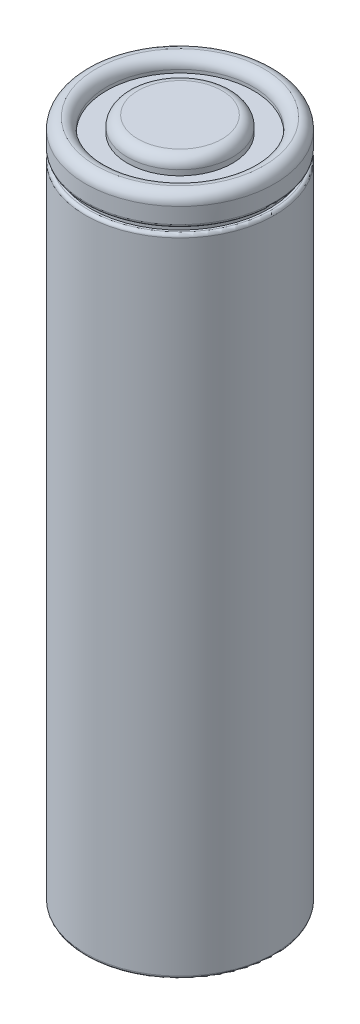
SolidWorks part; units mm, degrees
material "Chrome Stainless Steel"
ref_plane "Front Plane" through (0, 0, 0) normal (0, 0, 1) x (1, 0, 0)
ref_plane "Top Plane" through (0, 0, 0) normal (0, 1, 0) x (1, 0, 0)
ref_plane "Right Plane" through (0, 0, 0) normal (1, 0, 0) x (0, 0, -1)
sketch "Sketch1" plane through (0, 0, 0) normal (0, 1, 0) x (1, 0, 0)
  circle A0 centre (0, 0) radius 9
  dimension "D1" = 18
extrude "Boss-Extrude1" add sketch "Sketch1" along normal blind 65
sketch "Sketch2" plane through (0, 0, 0) normal (0, 0, 1) x (1, 0, 0)
  line L1 (0, 65) -> (0, 0) construction
  line L2 (9, 65) -> (-9, 65) construction
  line L3 (5, 65) -> (5, 63.5)
  line L4 (5, 63.5) -> (7, 63.5)
  line L5 (9, 0) -> (9, 65) construction
  line L6 (7, 63.5) -> (7, 64.8)
  line L7 (8.5, 62) -> (9, 62)
  line L8 (8.5, 62) -> (8.5, 61.5)
  line L9 (8.5, 61.5) -> (9, 61.5)
  line L10 (9, 62) -> (9, 61.5)
  line L11 (7, 64.8) -> (9, 64.8)
  line L12 (9, 64.8) -> (9, 65)
  line L13 (9, 65) -> (5, 65)
  dimension "D1" = 0.5
  dimension "D2" = 0.5
  dimension "D3" = 3
  dimension "D4" = 4
  dimension "D5" = 2
  dimension "D6" = 1.5
  dimension "D7" = 0.2
revolve "Cut-Revolve1" cut sketch "Sketch2" angle 360 about L1
fillet "Fillet1" radius 1 3 edges at (0, 65, 5) (0, 64.8, 7) (0, 64.8, 9)
fillet "Fillet2" radius 0.3 3 edges at (0, 0, 9) (0, 61.5, 9) (0, 62, 9)
equation "\"ABS_thickness\" = 1.59 "
equation "\"Bus_bar_thickness\" = 3.175"
equation "\"Connector_width\" = 20.2"
equation "\"Number_of_cells_long\" = 25"
equation "\"Number_of_cells_wide\" = 2"
equation "\"Cell_height\" = 65.0"
equation "\"D1@Sketch1\"  = \"Cell_diam\""
equation "\"Cell_diam\" = 18.0"
equation "\"D1@Boss-Extrude1\"=\"Cell_height\""
